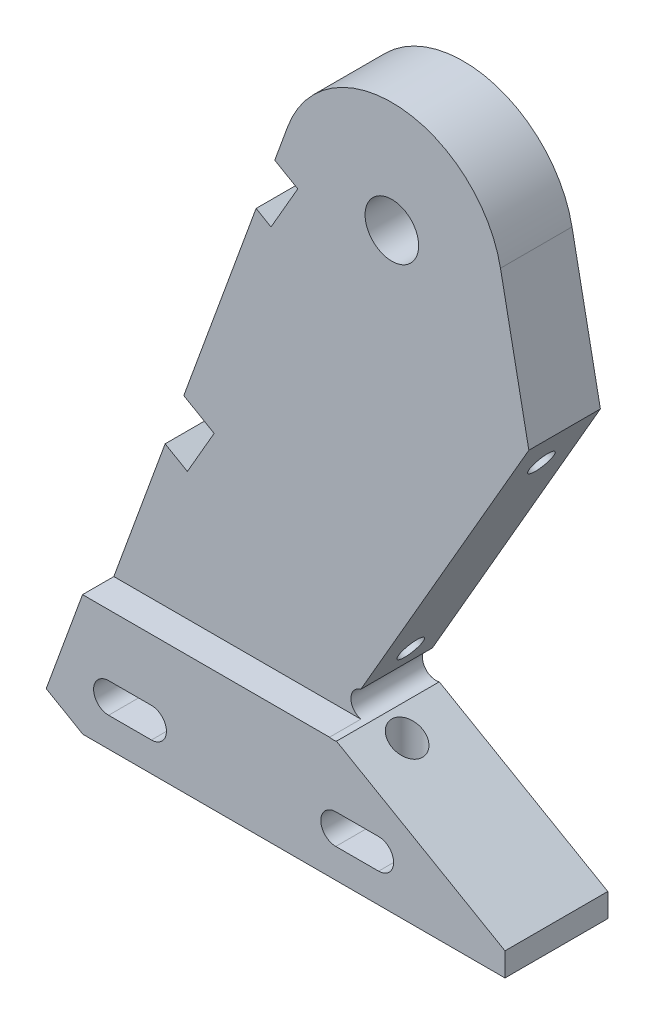
SolidWorks part; units mm, degrees
ref_plane "Front Plane" through (0, 0, 0) normal (0, 0, 1) x (1, 0, 0)
ref_plane "Top Plane" through (0, 0, 0) normal (0, 1, 0) x (1, 0, 0)
ref_plane "Right Plane" through (0, 0, 0) normal (1, 0, 0) x (0, 0, -1)
sketch "Model" plane through (0, 0, 0) normal (0, 0, 1) x (1, 0, 0)
  line L0 (30.032, -29.5212) -> (30.032, -26.7298)
  line L1 (-3.1895, 31.0479) -> (-11.7681, 7.5374)
  line L2 (12.4426, -6.5562) -> (9.2271, -12.1257) construction
  line L3 (16.6788, -19.0204) -> (10.0488, -15.1925) construction
  line L4 (9.6915, -11.3213) -> (10.8533, -15.657) construction
  line L5 (10.2724, -13.4891) -> (9.0035, -13.8291) construction
  line L6 (29.1519, 22.385) -> (9.2271, -12.1257)
  line L7 (30.032, -26.7298) -> (10.0488, -15.1925)
  line L8 (9.3745, -14.8032) -> (2.5284, -10.8506) construction
  line L9 (9.0235, -12.4784) -> (5.2305, -19.0481) construction
  line L10 (0.5709, 41.3535) -> (-0.9796, 37.1044)
  line L11 (0.0253, 32.858) -> (-15.4747, 6.0112) construction
  line L12 (-11.7681, 7.5374) -> (-8.1659, 5.4577)
  line L13 (-15.4747, 6.0112) -> (10.9052, -9.2192) construction
  line L14 (-11.7681, 7.5374) -> (-13.8872, 8.7609) construction
  line L15 (-11.3408, -0.0416) -> (-13.978, 1.4809) construction
  line L16 (-8.1659, 5.4577) -> (-11.3408, -0.0416)
  line L17 (-11.3408, -0.0416) -> (-13.978, 1.4809)
  line L18 (-13.978, 1.4809) -> (-24.3737, -27.0097)
  line L19 (0.0253, 32.858) -> (26.4052, 17.6276) construction
  line L20 (-1.4214, 30.0271) -> (1.7536, 35.5264)
  line L21 (-0.9796, 37.1044) -> (1.7536, 35.5264)
  line L22 (-3.1895, 31.0479) -> (-1.4214, 30.0271)
  line L23 (11.3113, 26.3421) -> (-4.1887, -0.5047) construction
  line L24 (3.5613, 12.9187) -> (-2.5691, 16.458) construction
  line L25 (12.2357, 35.6885) -> (0.2074, 14.855) construction
  line L26 (0.2074, 14.855) -> (12.9074, 36.8521) construction
  line L28 (29.1519, 22.385) -> (25.7905, 39.3975)
  line L80 (-20.0226, -29.5212) -> (-24.3737, -27.0097)
  line L82 (30.032, -29.5212) -> (-20.0226, -29.5212)
  circle A0 centre (12.9074, 36.8521) radius 3.175
  arc A2 (9.2271, -12.1257) -> (10.0488, -15.1925) centre (9.638, -13.6591) ccw
  arc A3 (25.7905, 39.3975) -> (0.5709, 41.3535) centre (12.9074, 36.8521) ccw
  point P11 (8.1045, -14.07)
  point P12 (8.1045, -14.07)
  point P37 (0.1661, 32.7767)
  dimension "D1" = 3.175
  dimension "D7" = 6.35
  dimension "D2" = 31
  dimension "D3" = 3.175
  dimension "D4" = 3.175
  dimension "D5" = 6.35
  dimension "D6" = 25.4
extrude "Boss-Extrude1" add sketch "Model" along normal blind 8.4836
sketch "Sketch2" plane through (0, 0, 8.4836) normal (0, 0, 1) x (1, 0, 0)
  line L0 (-32.0034, -15.1956) -> (9.2387, -15.1956) construction
  line L1 (-20.0226, -29.5212) -> (30.032, -29.5212) construction
  line L2 (-20.063, -15.1956) -> (9.2274, -15.1926)
  line L3 (-13.978, 1.4809) -> (-24.3737, -27.0097) construction
  line L4 (10.0488, -15.1925) -> (30.032, -26.7298)
  line L5 (30.032, -26.7298) -> (30.032, -29.5212)
  line L6 (30.032, -29.5212) -> (-20.0226, -29.5212)
  line L7 (-20.0226, -29.5212) -> (-24.3737, -27.0097)
  line L8 (-24.3737, -27.0097) -> (-20.063, -15.1956)
  line L9 (10.0372, -15.1956) -> (54.6863, -15.1956) construction
  line L10 (30.032, -29.5212) -> (30.032, -26.7298) construction
  arc A0 (9.2274, -15.1926) -> (10.0488, -15.1925) centre (9.638, -13.6591) ccw
  dimension "D1" = 14.3256
extrude "Boss-Extrude2" add sketch "Sketch2" along normal blind 3.7084
hole_wizard "#4 Clearance Hole3" positions "Sketch8" profile "Sketch9" hole size "#4" standard "ANSI Inch" end condition through all
sketch "Sketch8" plane through (-14.0682, 8.1223, 0) normal (-0.866, 0.5, 0) x (0, 0, 1)
  line L0 (8.4836, 25.2935) -> (0, 31.6435) construction
  point P7 (4.2418, 28.4685)
sketch "Sketch9" plane through (0.1661, 32.7767, 4.2418) normal (0, 0, 1) x (-0.5, -0.866, 0)
  line L0 (0, 0) -> (0, 57.0136)
  line L1 (0, 57.0136) -> (1.4732, 57.0136)
  line L2 (1.4732, 57.0136) -> (1.4732, 0)
  line L5 (1.4732, 0) -> (0, 0)
  line L11 (0, -6.35) -> (0, 107.95) construction
  dimension "Thru Hole Dia." = 2.9464
  dimension "Thru Hole Depth" = 57.0136
hole_wizard "#4 Clearance Hole4" positions "Sketch10" profile "Sketch11" hole size "#4" standard "ANSI Inch" end condition through all
sketch "Sketch10" plane through (-8.4878, 4.9001, 0) normal (-0.866, 0.5, 0) x (0, 0, 1)
  line L0 (0, 0.6438) -> (8.4836, -5.7062) construction
  point P7 (4.2418, -2.5312)
sketch "Sketch11" plane through (-9.7533, 2.708, 4.2418) normal (0, 0, 1) x (-0.5, -0.866, 0)
  line L0 (0, 0) -> (0, 50.5695)
  line L1 (0, 50.5695) -> (1.4732, 50.5695)
  line L2 (1.4732, 50.5695) -> (1.4732, 0)
  line L5 (1.4732, 0) -> (0, 0)
  line L11 (0, -6.35) -> (0, 107.95) construction
  dimension "Thru Hole Dia." = 2.9464
  dimension "Thru Hole Depth" = 50.5695
sketch "Sketch12" plane through (0, 0, 0) normal (0, 0, -1) x (-1, 0, 0)
  line L1 (-15.0462, -24.2634) -> (-9.9662, -24.2634) construction
  line L2 (-15.0462, -22.4854) -> (-9.9662, -22.4854)
  line L3 (-15.0462, -26.0414) -> (-9.9662, -26.0414)
  line L5 (11.8946, -24.2634) -> (16.9746, -24.2634) construction
  line L6 (11.8946, -22.4854) -> (16.9746, -22.4854)
  line L7 (11.8946, -26.0414) -> (16.9746, -26.0414)
  arc A0 (-15.0462, -22.4854) -> (-15.0462, -26.0414) centre (-15.0462, -24.2634) ccw
  arc A1 (-9.9662, -26.0414) -> (-9.9662, -22.4854) centre (-9.9662, -24.2634) ccw
  arc A2 (11.8946, -22.4854) -> (11.8946, -26.0414) centre (11.8946, -24.2634) ccw
  arc A3 (16.9746, -26.0414) -> (16.9746, -22.4854) centre (16.9746, -24.2634) ccw
  point P6 (-12.5062, -24.2634)
  point P18 (14.4346, -24.2634)
  dimension "D1" = 1.778
  dimension "D2" = 1.778
  dimension "D3" = 14.9858
extrude "Cut-Extrude1" cut sketch "Sketch12" against normal through all
hole_wizard "#6 Clearance Hole1" positions "Sketch13" profile "Sketch14" hole size "#6" standard "ANSI Inch"
sketch "Sketch13" plane through (0, -29.5212, 0) normal (0, -1, 0) x (-1, 0, 0)
  point P0 (14.4338, -6.2714)
  point P3 (-12.5069, -6.2714)
sketch "Sketch14" plane through (-14.4338, -29.5212, 6.2714) normal (1, 0, 0) x (0, 0, -1)
  line L0 (0, 0) -> (0, 15.425)
  line L1 (0, 15.425) -> (1.8288, 14.3262)
  line L2 (1.8288, 14.3262) -> (1.8288, 0)
  line L5 (1.8288, 0) -> (0, 0)
  line L10 (0, 15.425) -> (-1.8288, 14.3262) construction
  line L11 (0, -6.35) -> (0, 107.95) construction
  dimension "Hole Dia." = 3.6576
  dimension "Hole Depth" = 14.3262
  dimension "Drill Angle" = 118
